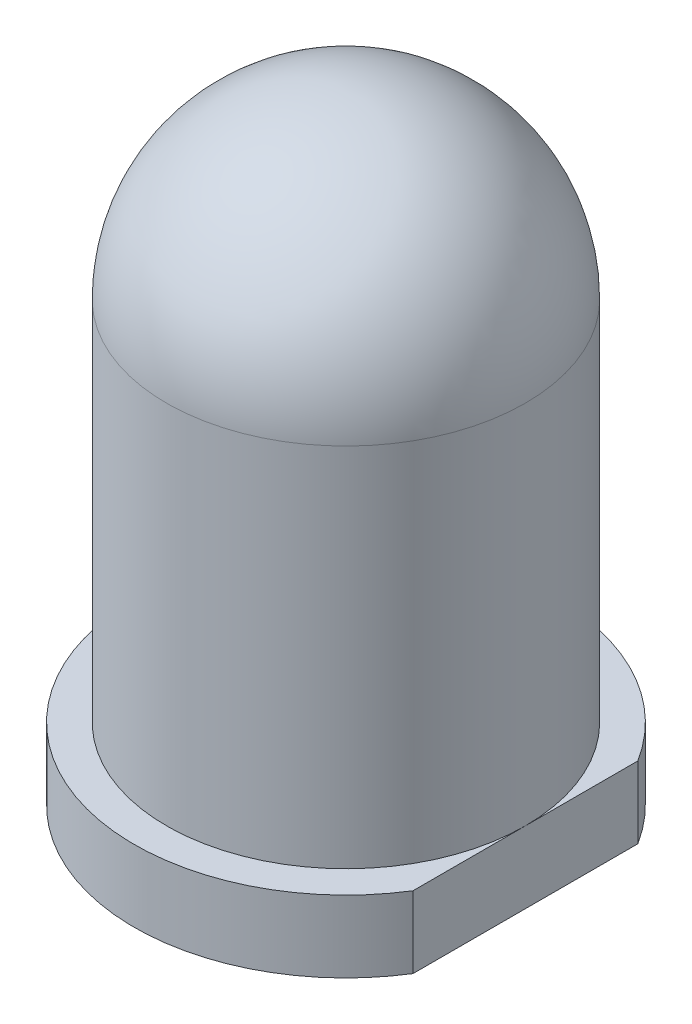
SolidWorks part; units mm, degrees
ref_plane "Front Plane" through (0, 0, 0) normal (0, 0, 1) x (1, 0, 0)
ref_plane "Top Plane" through (0, 0, 0) normal (0, 1, 0) x (1, 0, 0)
ref_plane "Right Plane" through (0, 0, 0) normal (1, 0, 0) x (0, 0, -1)
sketch "Sketch1" plane through (0, 0, 0) normal (0, 0, 1) x (1, 0, 0)
  line L0 (0, -170.0139) -> (0, 8330.6815) construction
  line L1 (2.5, 4.0232) -> (2.5, -1.0768)
  line L2 (2.5, -1.0768) -> (0, -1.0768)
  line L3 (0, 6.5232) -> (0, -1.0768)
  arc A0 (0, 6.5232) -> (2.5, 4.0232) centre (0, 4.0232) cw
  dimension "D1" = 2.5
  dimension "D2" = 7.6
revolve "Revolve1" add sketch "Sketch1" angle 360 about L0
sketch "Sketch2" plane through (0, -1.0768, 0) normal (0, -1, 0) x (1, 0, 0)
  line L0 (2.5, -1.566) -> (2.5, 1.566)
  arc A0 (2.5, 1.566) -> (2.5, -1.566) centre (0, 0) ccw
  circle A1 centre (0, 0) radius 2.5 construction
  dimension "D1" = 2.95
extrude "Boss-Extrude1" add sketch "Sketch2" along normal blind 1
ref_axis "Center line" through (0, 4.0232, 0) along (0, -1, 0)
